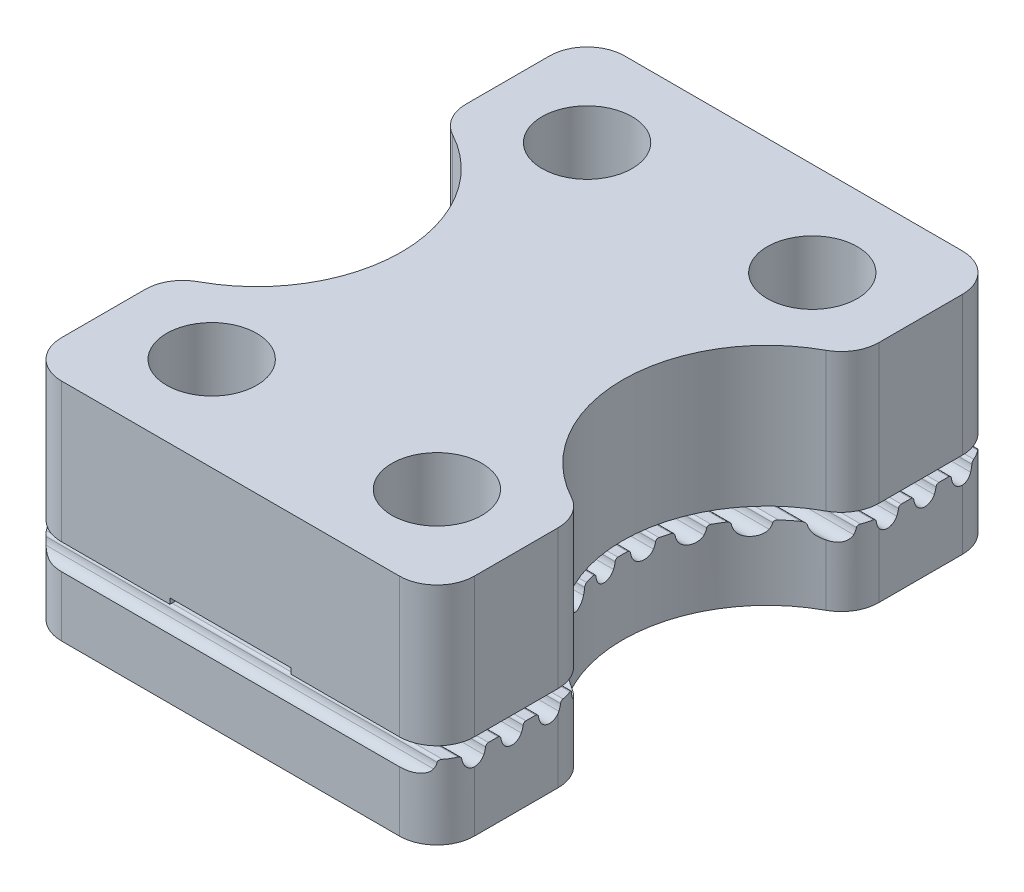
SolidWorks part; units mm, degrees
ref_plane "Front Plane" through (0, 0, 0) normal (0, 0, 1) x (1, 0, 0)
ref_plane "Top Plane" through (0, 0, 0) normal (0, 1, 0) x (1, 0, 0)
ref_plane "Right Plane" through (0, 0, 0) normal (1, 0, 0) x (0, 0, -1)
sketch "Sketch1" plane through (0, 0, 0) normal (0, 1, 0) x (1, 0, 0)
  line L0 (0, 0) -> (0, 15) construction
  line L1 (-11, -15) -> (11, -15)
  line L2 (-11, -15) -> (-11, -7.25)
  line L3 (-11, 15) -> (11, 15)
  line L4 (11, -15) -> (11, -7.25)
  line L5 (-11, -15) -> (11, 15) construction
  line L6 (-11, 15) -> (11, -15) construction
  line L7 (0, 0) -> (5.8937, 0) construction
  line L8 (-3.125, 15) -> (-3.125, -15) construction
  line L9 (3.125, 15) -> (3.125, -15) construction
  line L10 (-11, 7.25) -> (-11, 15)
  line L11 (11, 7.25) -> (11, 15)
  circle A0 centre (-6, 10) radius 2 construction
  arc A1 (-11, -7.25) -> (-11, 7.25) centre (-13.5937, 0) ccw
  arc A2 (11, -7.25) -> (11, 7.25) centre (13.5937, 0) cw
  point P0 (0, 0)
  point P5 (-6, 10)
  point P6 (6, 10)
  point P8 (6, -10)
  point P9 (-6, -10)
  dimension "D1" = 20
  dimension "D3" = 4
  dimension "D5" = 22
  dimension "D7" = 7.7
  dimension "D2" = 12
  dimension "D4" = 6.25
  dimension "D6" = 30
  dimension "D8" = 14.5
extrude "Boss-Extrude1" add sketch "Sketch1" against normal blind 12
sketch "Sketch2" plane through (0, 0, 0) normal (1, 0, 0) x (0, 0, -1)
  line L0 (-15, -7.42) -> (15, -7.42)
  line L1 (-15, -12) -> (-15, 0) construction
  line L2 (15, -12) -> (15, 0) construction
  line L3 (7.25, 0) -> (15, 0) construction
  line L4 (-14, -7.42) -> (-14, -10.333) construction
  line L5 (-14.2598, -8.05) -> (-14, -8.05)
  line L6 (-16, -10.333) -> (-16, -7.42) construction
  line L7 (-15.7402, -8.05) -> (-16, -8.05)
  line L8 (-13.7402, -8.05) -> (-14, -8.05)
  line L36 (-15, -7.42) -> (-16, -7.42)
  line L37 (-16, -7.42) -> (-16, -8.05)
  line L38 (15, -7.42) -> (14, -7.42)
  line L40 (-12.2598, -8.05) -> (-12, -8.05) [skipped]
  line L41 (-11.7402, -8.05) -> (-12, -8.05) [skipped]
  line L42 (-10.2598, -8.05) -> (-10, -8.05) [skipped]
  line L43 (-9.7402, -8.05) -> (-10, -8.05) [skipped]
  line L44 (-8.2598, -8.05) -> (-8, -8.05) [skipped]
  line L45 (-7.7402, -8.05) -> (-8, -8.05) [skipped]
  line L46 (-6.2598, -8.05) -> (-6, -8.05) [skipped]
  line L47 (-5.7402, -8.05) -> (-6, -8.05) [skipped]
  line L48 (-4.2598, -8.05) -> (-4, -8.05) [skipped]
  line L49 (-3.7402, -8.05) -> (-4, -8.05) [skipped]
  line L50 (-2.2598, -8.05) -> (-2, -8.05) [skipped]
  line L51 (-1.7402, -8.05) -> (-2, -8.05) [skipped]
  line L52 (-0.2598, -8.05) -> (0, -8.05) [skipped]
  line L53 (0.2598, -8.05) -> (0, -8.05) [skipped]
  line L54 (1.7402, -8.05) -> (2, -8.05) [skipped]
  line L55 (2.2598, -8.05) -> (2, -8.05) [skipped]
  line L56 (3.7402, -8.05) -> (4, -8.05) [skipped]
  line L57 (4.2598, -8.05) -> (4, -8.05) [skipped]
  line L58 (5.7402, -8.05) -> (6, -8.05) [skipped]
  line L59 (6.2598, -8.05) -> (6, -8.05) [skipped]
  line L60 (7.7402, -8.05) -> (8, -8.05) [skipped]
  line L61 (8.2598, -8.05) -> (8, -8.05) [skipped]
  line L62 (9.7402, -8.05) -> (10, -8.05) [skipped]
  line L63 (10.2598, -8.05) -> (10, -8.05) [skipped]
  line L64 (11.7402, -8.05) -> (12, -8.05) [skipped]
  line L65 (12.2598, -8.05) -> (12, -8.05) [skipped]
  line L66 (13.7402, -8.05) -> (14, -8.05) [skipped]
  line L67 (-13.7402, -8.05) -> (-14, -8.05)
  line L68 (-12.2598, -8.05) -> (-12, -8.05)
  line L69 (-11.7402, -8.05) -> (-12, -8.05)
  line L70 (-10.2598, -8.05) -> (-10, -8.05)
  line L71 (-9.7402, -8.05) -> (-10, -8.05)
  line L72 (-8.2598, -8.05) -> (-8, -8.05)
  line L73 (-7.7402, -8.05) -> (-8, -8.05)
  line L74 (-6.2598, -8.05) -> (-6, -8.05)
  line L75 (-5.7402, -8.05) -> (-6, -8.05)
  line L76 (-4.2598, -8.05) -> (-4, -8.05)
  line L77 (-3.7402, -8.05) -> (-4, -8.05)
  line L78 (-2.2598, -8.05) -> (-2, -8.05)
  line L79 (-1.7402, -8.05) -> (-2, -8.05)
  line L80 (-0.2598, -8.05) -> (0, -8.05)
  line L81 (0.2598, -8.05) -> (0, -8.05)
  line L82 (1.7402, -8.05) -> (2, -8.05)
  line L83 (2.2598, -8.05) -> (2, -8.05)
  line L84 (3.7402, -8.05) -> (4, -8.05)
  line L85 (4.2598, -8.05) -> (4, -8.05)
  line L86 (5.7402, -8.05) -> (6, -8.05)
  line L87 (6.2598, -8.05) -> (6, -8.05)
  line L88 (7.7402, -8.05) -> (8, -8.05)
  line L89 (8.2598, -8.05) -> (8, -8.05)
  line L90 (9.7402, -8.05) -> (10, -8.05)
  line L91 (10.2598, -8.05) -> (10, -8.05)
  line L92 (11.7402, -8.05) -> (12, -8.05)
  line L93 (12.2598, -8.05) -> (12, -8.05)
  line L94 (13.7402, -8.05) -> (14, -8.05)
  line L95 (14.2598, -8.05) -> (14, -8.05)
  line L96 (15.7402, -8.05) -> (16, -8.05)
  line L97 (16, -8.05) -> (15, -7.42)
  arc A0 (-15.4989, -8.4882) -> (-14.5011, -8.4882) centre (-15, -8.245) ccw
  arc A1 (-15.4989, -8.4882) -> (-15.5915, -8.1804) centre (-14.6, -8.05) cw
  arc A2 (-14.5011, -8.4882) -> (-14.4085, -8.1804) centre (-15.4, -8.05) ccw
  arc A3 (-14.4085, -8.1804) -> (-14.2598, -8.05) centre (-14.2598, -8.2) cw
  arc A4 (-15.5915, -8.1804) -> (-15.7402, -8.05) centre (-15.7402, -8.2) ccw
  arc A75 (-13.4989, -8.4882) -> (-13.5915, -8.1804) centre (-12.6, -8.05) cw [skipped]
  arc A76 (-13.4989, -8.4882) -> (-12.5011, -8.4882) centre (-13, -8.245) ccw [skipped]
  arc A77 (-12.5011, -8.4882) -> (-12.4085, -8.1804) centre (-13.4, -8.05) ccw [skipped]
  arc A78 (-12.4085, -8.1804) -> (-12.2598, -8.05) centre (-12.2598, -8.2) cw [skipped]
  arc A79 (-11.5915, -8.1804) -> (-11.7402, -8.05) centre (-11.7402, -8.2) ccw [skipped]
  arc A80 (-11.4989, -8.4882) -> (-11.5915, -8.1804) centre (-10.6, -8.05) cw [skipped]
  arc A81 (-11.4989, -8.4882) -> (-10.5011, -8.4882) centre (-11, -8.245) ccw [skipped]
  arc A82 (-10.5011, -8.4882) -> (-10.4085, -8.1804) centre (-11.4, -8.05) ccw [skipped]
  arc A83 (-10.4085, -8.1804) -> (-10.2598, -8.05) centre (-10.2598, -8.2) cw [skipped]
  arc A84 (-9.5915, -8.1804) -> (-9.7402, -8.05) centre (-9.7402, -8.2) ccw [skipped]
  arc A85 (-9.4989, -8.4882) -> (-9.5915, -8.1804) centre (-8.6, -8.05) cw [skipped]
  arc A86 (-13.5915, -8.1804) -> (-13.7402, -8.05) centre (-13.7402, -8.2) ccw [skipped]
  arc A87 (-9.4989, -8.4882) -> (-8.5011, -8.4882) centre (-9, -8.245) ccw [skipped]
  arc A88 (-8.5011, -8.4882) -> (-8.4085, -8.1804) centre (-9.4, -8.05) ccw [skipped]
  arc A89 (-8.4085, -8.1804) -> (-8.2598, -8.05) centre (-8.2598, -8.2) cw [skipped]
  arc A90 (-7.5915, -8.1804) -> (-7.7402, -8.05) centre (-7.7402, -8.2) ccw [skipped]
  arc A91 (-7.4989, -8.4882) -> (-7.5915, -8.1804) centre (-6.6, -8.05) cw [skipped]
  arc A92 (-7.4989, -8.4882) -> (-6.5011, -8.4882) centre (-7, -8.245) ccw [skipped]
  arc A93 (-6.5011, -8.4882) -> (-6.4085, -8.1804) centre (-7.4, -8.05) ccw [skipped]
  arc A94 (-6.4085, -8.1804) -> (-6.2598, -8.05) centre (-6.2598, -8.2) cw [skipped]
  arc A95 (-5.5915, -8.1804) -> (-5.7402, -8.05) centre (-5.7402, -8.2) ccw [skipped]
  arc A96 (-5.4989, -8.4882) -> (-5.5915, -8.1804) centre (-4.6, -8.05) cw [skipped]
  arc A97 (-5.4989, -8.4882) -> (-4.5011, -8.4882) centre (-5, -8.245) ccw [skipped]
  arc A98 (-4.5011, -8.4882) -> (-4.4085, -8.1804) centre (-5.4, -8.05) ccw [skipped]
  arc A99 (-4.4085, -8.1804) -> (-4.2598, -8.05) centre (-4.2598, -8.2) cw [skipped]
  arc A100 (-3.5915, -8.1804) -> (-3.7402, -8.05) centre (-3.7402, -8.2) ccw [skipped]
  arc A101 (-3.4989, -8.4882) -> (-3.5915, -8.1804) centre (-2.6, -8.05) cw [skipped]
  arc A102 (-3.4989, -8.4882) -> (-2.5011, -8.4882) centre (-3, -8.245) ccw [skipped]
  arc A103 (-2.5011, -8.4882) -> (-2.4085, -8.1804) centre (-3.4, -8.05) ccw [skipped]
  arc A104 (-2.4085, -8.1804) -> (-2.2598, -8.05) centre (-2.2598, -8.2) cw [skipped]
  arc A105 (-1.5915, -8.1804) -> (-1.7402, -8.05) centre (-1.7402, -8.2) ccw [skipped]
  arc A106 (-1.4989, -8.4882) -> (-1.5915, -8.1804) centre (-0.6, -8.05) cw [skipped]
  arc A107 (-1.4989, -8.4882) -> (-0.5011, -8.4882) centre (-1, -8.245) ccw [skipped]
  arc A108 (-0.5011, -8.4882) -> (-0.4085, -8.1804) centre (-1.4, -8.05) ccw [skipped]
  arc A109 (-0.4085, -8.1804) -> (-0.2598, -8.05) centre (-0.2598, -8.2) cw [skipped]
  arc A110 (0.4085, -8.1804) -> (0.2598, -8.05) centre (0.2598, -8.2) ccw [skipped]
  arc A111 (0.5011, -8.4882) -> (0.4085, -8.1804) centre (1.4, -8.05) cw [skipped]
  arc A112 (0.5011, -8.4882) -> (1.4989, -8.4882) centre (1, -8.245) ccw [skipped]
  arc A113 (1.4989, -8.4882) -> (1.5915, -8.1804) centre (0.6, -8.05) ccw [skipped]
  arc A114 (1.5915, -8.1804) -> (1.7402, -8.05) centre (1.7402, -8.2) cw [skipped]
  arc A115 (2.4085, -8.1804) -> (2.2598, -8.05) centre (2.2598, -8.2) ccw [skipped]
  arc A116 (2.5011, -8.4882) -> (2.4085, -8.1804) centre (3.4, -8.05) cw [skipped]
  arc A117 (2.5011, -8.4882) -> (3.4989, -8.4882) centre (3, -8.245) ccw [skipped]
  arc A118 (3.4989, -8.4882) -> (3.5915, -8.1804) centre (2.6, -8.05) ccw [skipped]
  arc A119 (3.5915, -8.1804) -> (3.7402, -8.05) centre (3.7402, -8.2) cw [skipped]
  arc A120 (4.4085, -8.1804) -> (4.2598, -8.05) centre (4.2598, -8.2) ccw [skipped]
  arc A121 (4.5011, -8.4882) -> (4.4085, -8.1804) centre (5.4, -8.05) cw [skipped]
  arc A122 (4.5011, -8.4882) -> (5.4989, -8.4882) centre (5, -8.245) ccw [skipped]
  arc A123 (5.4989, -8.4882) -> (5.5915, -8.1804) centre (4.6, -8.05) ccw [skipped]
  arc A124 (5.5915, -8.1804) -> (5.7402, -8.05) centre (5.7402, -8.2) cw [skipped]
  arc A125 (6.4085, -8.1804) -> (6.2598, -8.05) centre (6.2598, -8.2) ccw [skipped]
  arc A126 (6.5011, -8.4882) -> (6.4085, -8.1804) centre (7.4, -8.05) cw [skipped]
  arc A127 (6.5011, -8.4882) -> (7.4989, -8.4882) centre (7, -8.245) ccw [skipped]
  arc A128 (7.4989, -8.4882) -> (7.5915, -8.1804) centre (6.6, -8.05) ccw [skipped]
  arc A129 (7.5915, -8.1804) -> (7.7402, -8.05) centre (7.7402, -8.2) cw [skipped]
  arc A130 (8.4085, -8.1804) -> (8.2598, -8.05) centre (8.2598, -8.2) ccw [skipped]
  arc A131 (8.5011, -8.4882) -> (8.4085, -8.1804) centre (9.4, -8.05) cw [skipped]
  arc A132 (8.5011, -8.4882) -> (9.4989, -8.4882) centre (9, -8.245) ccw [skipped]
  arc A133 (9.4989, -8.4882) -> (9.5915, -8.1804) centre (8.6, -8.05) ccw [skipped]
  arc A134 (9.5915, -8.1804) -> (9.7402, -8.05) centre (9.7402, -8.2) cw [skipped]
  arc A135 (10.4085, -8.1804) -> (10.2598, -8.05) centre (10.2598, -8.2) ccw [skipped]
  arc A136 (10.5011, -8.4882) -> (10.4085, -8.1804) centre (11.4, -8.05) cw [skipped]
  arc A137 (10.5011, -8.4882) -> (11.4989, -8.4882) centre (11, -8.245) ccw [skipped]
  arc A138 (11.4989, -8.4882) -> (11.5915, -8.1804) centre (10.6, -8.05) ccw [skipped]
  arc A139 (11.5915, -8.1804) -> (11.7402, -8.05) centre (11.7402, -8.2) cw [skipped]
  arc A140 (12.4085, -8.1804) -> (12.2598, -8.05) centre (12.2598, -8.2) ccw [skipped]
  arc A141 (12.5011, -8.4882) -> (12.4085, -8.1804) centre (13.4, -8.05) cw [skipped]
  arc A142 (12.5011, -8.4882) -> (13.4989, -8.4882) centre (13, -8.245) ccw [skipped]
  arc A143 (13.4989, -8.4882) -> (13.5915, -8.1804) centre (12.6, -8.05) ccw [skipped]
  arc A144 (13.5915, -8.1804) -> (13.7402, -8.05) centre (13.7402, -8.2) cw [skipped]
  arc A145 (-13.5915, -8.1804) -> (-13.7402, -8.05) centre (-13.7402, -8.2) ccw
  arc A146 (-13.4989, -8.4882) -> (-13.5915, -8.1804) centre (-12.6, -8.05) cw
  arc A147 (-13.4989, -8.4882) -> (-12.5011, -8.4882) centre (-13, -8.245) ccw
  arc A148 (-12.5011, -8.4882) -> (-12.4085, -8.1804) centre (-13.4, -8.05) ccw
  arc A149 (-12.4085, -8.1804) -> (-12.2598, -8.05) centre (-12.2598, -8.2) cw
  arc A150 (-11.5915, -8.1804) -> (-11.7402, -8.05) centre (-11.7402, -8.2) ccw
  arc A151 (-11.4989, -8.4882) -> (-11.5915, -8.1804) centre (-10.6, -8.05) cw
  arc A152 (-11.4989, -8.4882) -> (-10.5011, -8.4882) centre (-11, -8.245) ccw
  arc A153 (-10.5011, -8.4882) -> (-10.4085, -8.1804) centre (-11.4, -8.05) ccw
  arc A154 (-10.4085, -8.1804) -> (-10.2598, -8.05) centre (-10.2598, -8.2) cw
  arc A155 (-9.5915, -8.1804) -> (-9.7402, -8.05) centre (-9.7402, -8.2) ccw
  arc A156 (-9.4989, -8.4882) -> (-9.5915, -8.1804) centre (-8.6, -8.05) cw
  arc A157 (-9.4989, -8.4882) -> (-8.5011, -8.4882) centre (-9, -8.245) ccw
  arc A158 (-8.5011, -8.4882) -> (-8.4085, -8.1804) centre (-9.4, -8.05) ccw
  arc A159 (-8.4085, -8.1804) -> (-8.2598, -8.05) centre (-8.2598, -8.2) cw
  arc A160 (-7.5915, -8.1804) -> (-7.7402, -8.05) centre (-7.7402, -8.2) ccw
  arc A161 (-7.4989, -8.4882) -> (-7.5915, -8.1804) centre (-6.6, -8.05) cw
  arc A162 (-7.4989, -8.4882) -> (-6.5011, -8.4882) centre (-7, -8.245) ccw
  arc A163 (-6.5011, -8.4882) -> (-6.4085, -8.1804) centre (-7.4, -8.05) ccw
  arc A164 (-6.4085, -8.1804) -> (-6.2598, -8.05) centre (-6.2598, -8.2) cw
  arc A165 (-5.5915, -8.1804) -> (-5.7402, -8.05) centre (-5.7402, -8.2) ccw
  arc A166 (-5.4989, -8.4882) -> (-5.5915, -8.1804) centre (-4.6, -8.05) cw
  arc A167 (-5.4989, -8.4882) -> (-4.5011, -8.4882) centre (-5, -8.245) ccw
  arc A168 (-4.5011, -8.4882) -> (-4.4085, -8.1804) centre (-5.4, -8.05) ccw
  arc A169 (-4.4085, -8.1804) -> (-4.2598, -8.05) centre (-4.2598, -8.2) cw
  arc A170 (-3.5915, -8.1804) -> (-3.7402, -8.05) centre (-3.7402, -8.2) ccw
  arc A171 (-3.4989, -8.4882) -> (-3.5915, -8.1804) centre (-2.6, -8.05) cw
  arc A172 (-3.4989, -8.4882) -> (-2.5011, -8.4882) centre (-3, -8.245) ccw
  arc A173 (-2.5011, -8.4882) -> (-2.4085, -8.1804) centre (-3.4, -8.05) ccw
  arc A174 (-2.4085, -8.1804) -> (-2.2598, -8.05) centre (-2.2598, -8.2) cw
  arc A175 (-1.5915, -8.1804) -> (-1.7402, -8.05) centre (-1.7402, -8.2) ccw
  arc A176 (-1.4989, -8.4882) -> (-1.5915, -8.1804) centre (-0.6, -8.05) cw
  arc A177 (-1.4989, -8.4882) -> (-0.5011, -8.4882) centre (-1, -8.245) ccw
  arc A178 (-0.5011, -8.4882) -> (-0.4085, -8.1804) centre (-1.4, -8.05) ccw
  arc A179 (-0.4085, -8.1804) -> (-0.2598, -8.05) centre (-0.2598, -8.2) cw
  arc A180 (0.4085, -8.1804) -> (0.2598, -8.05) centre (0.2598, -8.2) ccw
  arc A181 (0.5011, -8.4882) -> (0.4085, -8.1804) centre (1.4, -8.05) cw
  arc A182 (0.5011, -8.4882) -> (1.4989, -8.4882) centre (1, -8.245) ccw
  arc A183 (1.4989, -8.4882) -> (1.5915, -8.1804) centre (0.6, -8.05) ccw
  arc A184 (1.5915, -8.1804) -> (1.7402, -8.05) centre (1.7402, -8.2) cw
  arc A185 (2.4085, -8.1804) -> (2.2598, -8.05) centre (2.2598, -8.2) ccw
  arc A186 (2.5011, -8.4882) -> (2.4085, -8.1804) centre (3.4, -8.05) cw
  arc A187 (2.5011, -8.4882) -> (3.4989, -8.4882) centre (3, -8.245) ccw
  arc A188 (3.4989, -8.4882) -> (3.5915, -8.1804) centre (2.6, -8.05) ccw
  arc A189 (3.5915, -8.1804) -> (3.7402, -8.05) centre (3.7402, -8.2) cw
  arc A190 (4.4085, -8.1804) -> (4.2598, -8.05) centre (4.2598, -8.2) ccw
  arc A191 (4.5011, -8.4882) -> (4.4085, -8.1804) centre (5.4, -8.05) cw
  arc A192 (4.5011, -8.4882) -> (5.4989, -8.4882) centre (5, -8.245) ccw
  arc A193 (5.4989, -8.4882) -> (5.5915, -8.1804) centre (4.6, -8.05) ccw
  arc A194 (5.5915, -8.1804) -> (5.7402, -8.05) centre (5.7402, -8.2) cw
  arc A195 (6.4085, -8.1804) -> (6.2598, -8.05) centre (6.2598, -8.2) ccw
  arc A196 (6.5011, -8.4882) -> (6.4085, -8.1804) centre (7.4, -8.05) cw
  arc A197 (6.5011, -8.4882) -> (7.4989, -8.4882) centre (7, -8.245) ccw
  arc A198 (7.4989, -8.4882) -> (7.5915, -8.1804) centre (6.6, -8.05) ccw
  arc A199 (7.5915, -8.1804) -> (7.7402, -8.05) centre (7.7402, -8.2) cw
  arc A200 (8.4085, -8.1804) -> (8.2598, -8.05) centre (8.2598, -8.2) ccw
  arc A201 (8.5011, -8.4882) -> (8.4085, -8.1804) centre (9.4, -8.05) cw
  arc A202 (8.5011, -8.4882) -> (9.4989, -8.4882) centre (9, -8.245) ccw
  arc A203 (9.4989, -8.4882) -> (9.5915, -8.1804) centre (8.6, -8.05) ccw
  arc A204 (9.5915, -8.1804) -> (9.7402, -8.05) centre (9.7402, -8.2) cw
  arc A205 (10.4085, -8.1804) -> (10.2598, -8.05) centre (10.2598, -8.2) ccw
  arc A206 (10.5011, -8.4882) -> (10.4085, -8.1804) centre (11.4, -8.05) cw
  arc A207 (10.5011, -8.4882) -> (11.4989, -8.4882) centre (11, -8.245) ccw
  arc A208 (11.4989, -8.4882) -> (11.5915, -8.1804) centre (10.6, -8.05) ccw
  arc A209 (11.5915, -8.1804) -> (11.7402, -8.05) centre (11.7402, -8.2) cw
  arc A210 (12.4085, -8.1804) -> (12.2598, -8.05) centre (12.2598, -8.2) ccw
  arc A211 (12.5011, -8.4882) -> (12.4085, -8.1804) centre (13.4, -8.05) cw
  arc A212 (12.5011, -8.4882) -> (13.4989, -8.4882) centre (13, -8.245) ccw
  arc A213 (13.4989, -8.4882) -> (13.5915, -8.1804) centre (12.6, -8.05) ccw
  arc A214 (13.5915, -8.1804) -> (13.7402, -8.05) centre (13.7402, -8.2) cw
  arc A215 (14.4085, -8.1804) -> (14.2598, -8.05) centre (14.2598, -8.2) ccw
  arc A216 (14.5011, -8.4882) -> (14.4085, -8.1804) centre (15.4, -8.05) cw
  arc A217 (14.5011, -8.4882) -> (15.4989, -8.4882) centre (15, -8.245) ccw
  arc A218 (15.4989, -8.4882) -> (15.5915, -8.1804) centre (14.6, -8.05) ccw
  arc A219 (15.5915, -8.1804) -> (15.7402, -8.05) centre (15.7402, -8.2) cw
  point P11 (-14.6, -8.05)
  point P20 (-14.4, -8.05)
  dimension "D2" = 0.555
  dimension "D3" = 1.38
  dimension "D5" = 1
  dimension "D8" = 0.15
  dimension "D1" = 7.42
  dimension "D4" = 0.4
  dimension "D6" = 0.63
  dimension "D7" = 1
  dimension "D9" = 1
  dimension "D11" = 16
  dimension "D10" = 15
extrude "Cut-Extrude1" cut sketch "Sketch2" against normal through all both and the other way through all contours A218 A219 L96 L97 L0 L36 L37 L7 A4 A1 A0 A2 A3 L5 L8 A145 A146 A147 A148 A149 L68 L69 A150 A151 A152 A153 A154 L70 L71 A155 A156 A157 A158 A159 L72 L73 A160 A161 A162 A163 A164 L74 L75 A165 A166 A167 A168 A169 L76 L77 region at (0, -7.9705, 0.1567)
hole_wizard "M4 Clearance Hole1" positions "Sketch3" profile "Sketch4" hole size "M4" standard "ANSI Metric" end condition through all
sketch "Sketch3" plane through (0, 0, 0) normal (0, 1, 0) x (1, 0, 0)
  point P0 (6, -10)
  point P3 (-6, -10)
  point P6 (6, 10)
  point P9 (-6, 10)
sketch "Sketch4" plane through (6, 0, 10) normal (1, 0, 0) x (0, 0, 1)
  line L0 (0, 0) -> (0, 12)
  line L1 (0, 12) -> (2.4, 12)
  line L2 (2.4, 12) -> (2.4, 0)
  line L5 (2.4, 0) -> (0, 0)
  line L11 (0, -6.35) -> (0, 107.95) construction
  dimension "Thru Hole Dia." = 4.8
  dimension "Thru Hole Depth" = 12
sketch "Sketch5" plane through (0, 0, 0) normal (0, 0, 1) x (1, 0, 0)
  line L0 (-11, -7.42) -> (11, -7.42) construction
  line L1 (3.225, -7.42) -> (-3.225, -7.42)
  line L2 (3.225, -7.42) -> (3.225, -7.12)
  line L3 (3.225, -7.12) -> (-3.225, -7.12)
  line L4 (-3.225, -7.42) -> (-3.225, -7.12)
  point P6 (0, -7.12)
  dimension "D1" = 6.45
  dimension "D2" = 0.3
extrude "Cut-Extrude2" cut sketch "Sketch5" against normal through all both and the other way through all
fillet "Fillet1" radius 2 8 edges at (11, -3.71, -7.25) (-11, -3.71, 15) (-11, -3.71, 7.25) (-11, -3.71, -7.25) (-11, -3.71, -15) (11, -3.71, -15) (11, -3.71, 7.25) (11, -3.71, 15)
fillet "Fillet2" radius 2 8 edges at (11, -10.4, -15) (-11, -10.4, -15) (-11, -10.3703, -7.25) (-11, -10.3703, 7.25) (-11, -10.4, 15) (11, -10.3703, -7.25) (11, -10.3703, 7.25) (11, -10.4, 15)
